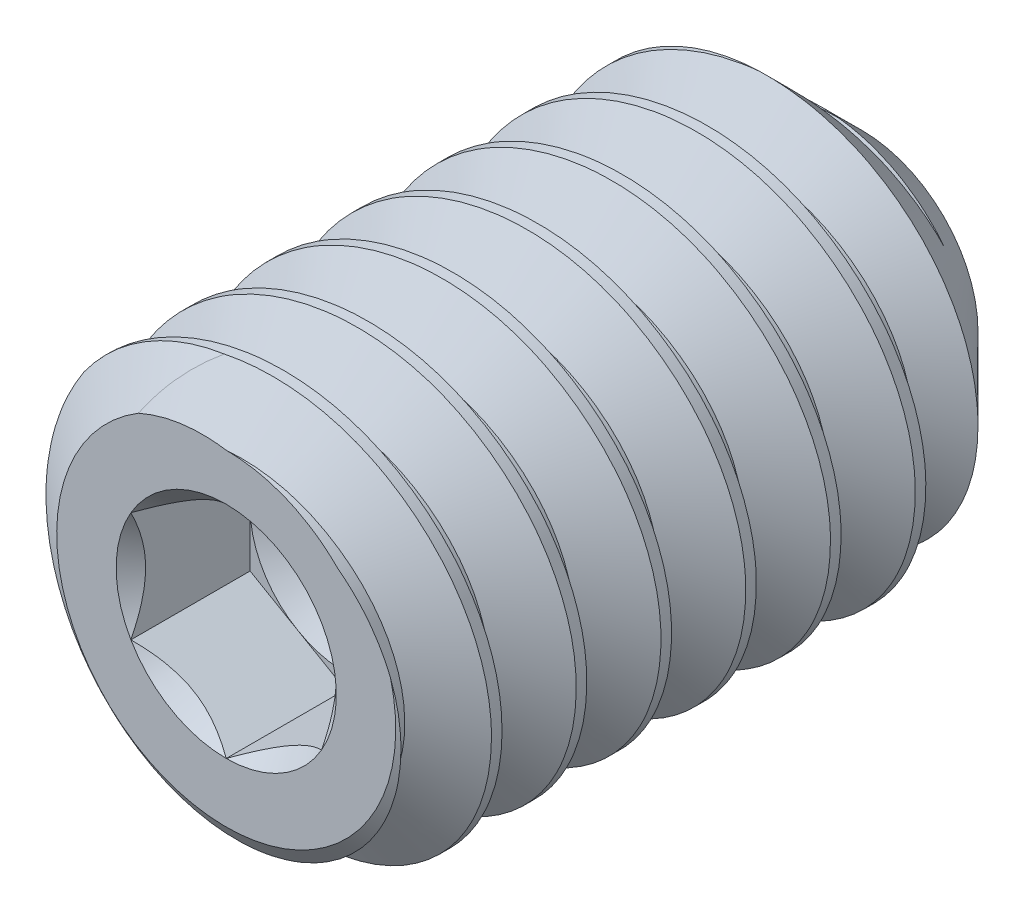
SolidWorks part; units mm, degrees
ref_plane "Front" through (0, 0, 0) normal (0, 0, 1) x (1, 0, 0)
ref_plane "Top" through (0, 0, 0) normal (0, 1, 0) x (1, 0, 0)
ref_plane "Right" through (0, 0, 0) normal (1, 0, 0) x (0, 0, -1)
sketch "Sketch22" plane through (0, 0, 0) normal (1, 0, 0) x (0, 0, -1)
  line L0 (-1.3354, 0) -> (-1.3354, 0.8)
  line L1 (-1.3354, 0.8) -> (-1.1953, 1)
  line L2 (-1.1953, 1) -> (1.2126, 1)
  line L3 (1.2126, 1) -> (1.6646, 0.548)
  line L4 (1.6646, 0.548) -> (1.3354, 0)
  line L5 (1.3354, 0) -> (-1.3354, 0)
  line L6 (1.3354, 0) -> (1.6646, 0) construction
  line L7 (1.6646, 0) -> (1.6646, 0.548) construction
  line L8 (1.6646, -0.548) -> (1.3354, 0) construction
  line L9 (-1.1953, -1) -> (1.2126, -1) construction
  dimension "Dia" = 2
  dimension "Length" = 3
  dimension "D3" = 35
  dimension "D5" = 118
  dimension "D6" = 45
  dimension "D7" = 1.6
revolve "Revolve1" add sketch "Sketch22" angle 360 about L6
ref_plane "Plane1" through (0, 0, -1.6646) normal (0, 0, 1) x (1, 0, 0)
sketch "Sketch27" plane through (0, 0, -1.6646) normal (0, 0, 1) x (1, 0, 0)
  circle A0 centre (0, 0) radius 1 construction
  circle A1 centre (0, 0) radius 1
curve "Helix/Spiral1" pitch 0.4 height 3.4 turns 8.5
sketch "Sketch28" plane through (0, 0, 0) normal (1, 0, 0) x (0, 0, -1)
  line L0 (1.6646, 1) -> (2.0146, 1)
  line L1 (2.0146, 1) -> (1.8646, 0.7402)
  line L2 (1.8646, 0.7402) -> (1.8146, 0.7402)
  line L3 (1.8146, 0.7402) -> (1.6646, 1)
  line L4 (1.7396, 0.8701) -> (1.9396, 0.8701) construction
  line L6 (-1.1953, 1) -> (1.2126, 1) construction
  dimension "D1" = 0.05
  dimension "D3" = 60
  dimension "D2" = 0.2
sweep "Cut-Sweep2" cut profiles "Sketch28" path "Helix/Spiral1" align with end faces yes
sketch "Sketch23" plane through (0, 0, 1.3354) normal (0, 0, 1) x (1, 0, 0)
  line L1 (0, 0.5196) -> (-0.45, 0.2598)
  line L2 (-0.45, 0.2598) -> (-0.45, -0.2598)
  line L3 (-0.45, -0.2598) -> (0, -0.5196)
  line L4 (0, -0.5196) -> (0.45, -0.2598)
  line L5 (0.45, -0.2598) -> (0.45, 0.2598)
  line L6 (0.45, 0.2598) -> (0, 0.5196)
  circle A0 centre (0, 0) radius 0.45 construction
  dimension "Hex" = 0.9
extrude "Cut-Extrude10" cut sketch "Sketch23" against normal blind 0.5625
sketch "Sketch24" plane through (0, 0, 1.3354) normal (0, 0, 1) x (1, 0, 0)
  circle A0 centre (0, 0) radius 0.5196
extrude "Cut-Extrude11" cut sketch "Sketch24" against normal through all draft 45
sketch "Sketch26" plane through (0, 0, 0.7729) normal (0, 0, 1) x (1, 0, 0)
  circle A0 centre (0, 0) radius 0.45 construction
  circle A1 centre (0, 0) radius 0.45
extrude "Cut-Extrude12" cut sketch "Sketch26" against normal through all draft 60
sketch "Sketch30" plane through (0, 0, 0) normal (1, 0, 0) x (0, 0, -1)
  line L0 (-1.1953, 1) -> (1.2126, 1) construction
  line L1 (-1.3354, 0) -> (-1.3354, 0.8) construction
  line L2 (1.6646, 0) -> (1.6646, 0.548) construction
  line L3 (-1.1953, -1) -> (1.2126, -1) construction
  point P0 (-1.3354, 1)
  point P1 (1.6646, 1)
  point P2 (1.6646, -1)
  point P11 (1.0646, -1)
  dimension "D1" = 0.6
sketch "Sketch31" plane through (0, 0, 0) normal (1, 0, 0) x (0, 0, -1)
  line L2 (1.3354, 0) -> (1.6646, -0.548)
  line L3 (1.6646, 0.548) -> (1.3354, 0)
equation "\"D7@Sketch22\"=\"Dia@Sketch22\"*.8"
equation "\"D1@Sketch28\" = \"D4@Helix/Spiral1\" * .125"
equation "\"D2@Sketch28\" = \"D4@Helix/Spiral1\" * .5"
equation "\"D3@Helix/Spiral1\" = \"Length@Sketch22\" + \"D4@Helix/Spiral1\""
equation "\"D1@Sketch30\" = \"D4@Helix/Spiral1\" * 1.5"
equation "\"hex Depth@Cut-Extrude10\" = \"Hex@Sketch23\" * .625"
